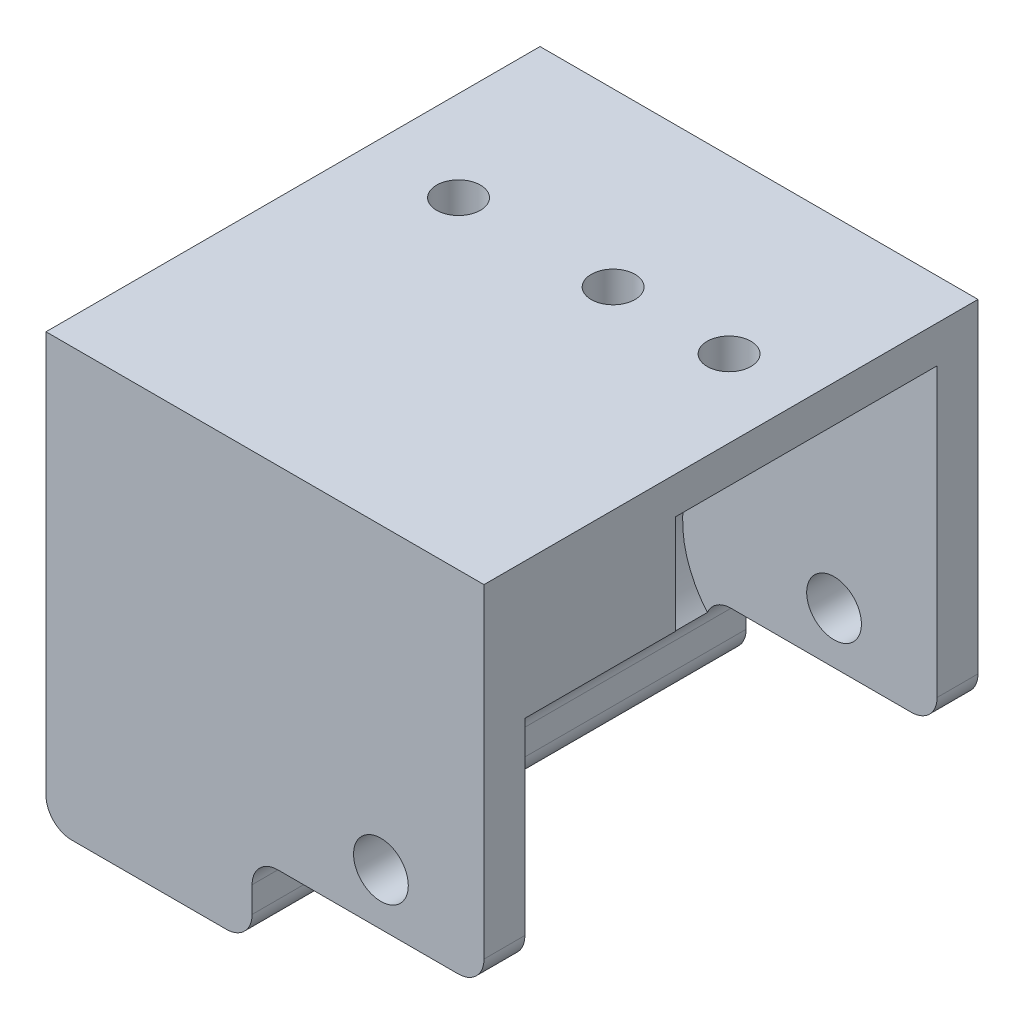
SolidWorks part; units mm, degrees
ref_plane "Front Plane" through (0, 0, 0) normal (0, 0, 1) x (1, 0, 0)
ref_plane "Top Plane" through (0, 0, 0) normal (0, 1, 0) x (1, 0, 0)
ref_plane "Right Plane" through (0, 0, 0) normal (1, 0, 0) x (0, 0, -1)
sketch "Sketch1" plane through (0, 0, 0) normal (0, 0, 1) x (1, 0, 0)
  line L0 (-18, 24) -> (-18, 0) construction
  line L5 (0, 0) -> (-18, 0)
  line L6 (0, 0) -> (0, 24)
  line L7 (0, 24) -> (-34, 24)
  line L8 (-34, 0) -> (-34, 24)
  line L11 (-34, 0) -> (-34, -6)
  line L12 (-34, -6) -> (-18, -6)
  line L13 (-18, 0) -> (-18, -6)
  circle A27 centre (-4, 19.15) radius 2.125 construction
  circle A28 centre (-12, 19.15) radius 2.125 construction
  circle A29 centre (-21, 19.15) radius 2.125 construction
  circle A30 centre (-8, 4) radius 2.125
  dimension "D3" = 4.25
  dimension "D7" = 8
  dimension "D8" = 4.25
  dimension "D1" = 4.25
  dimension "D2" = 4.25
  dimension "D4" = 4.85
  dimension "D5" = 9
  dimension "D9" = 4
  dimension "D6" = 4
  dimension "D10" = 4
  dimension "D11" = 24
  dimension "D12" = 13
  dimension "D13" = 16
  dimension "D14" = 30
extrude "Boss-Extrude1" add sketch "Sketch1" along normal blind 3.175
ref_plane "Plane1" through (0, 0, -16) normal (0, 0, -1) x (-1, 0, 0)
sketch "Sketch4" plane through (0, 24, 0) normal (0, 1, 0) x (1, 0, 0)
  line L0 (-34, 32) -> (0, 32) construction
  line L1 (-34, -3.175) -> (0, -3.175)
  line L2 (-34, -3.175) -> (-34, 35.175)
  line L3 (-34, 35.175) -> (0, 35.175)
  line L4 (0, -3.175) -> (0, 35.175)
  line L5 (0, 0) -> (-34, 0) construction
  dimension "D1" = 3.175
  dimension "D2" = 32
extrude "Boss-Extrude2" add sketch "Sketch4" along normal blind 3.175
mirror "Mirror2" about plane through (0, 0, -16) normal (0, 0, -1) of "Boss-Extrude1"
sketch "Sketch5" plane through (0, 0, 0) normal (0, 0, -1) x (-1, 0, 0)
  line L0 (0, 24) -> (34, 24) construction
  line L1 (0, 24) -> (34, 24) construction
  line L2 (18, 9) -> (18, 16.6)
  line L3 (34, -6) -> (18, -6)
  line L4 (34, -6) -> (34, 16.6)
  line L6 (18, -6) -> (18, -1)
  line L7 (18, 16.6) -> (34, 16.6)
  arc A1 (18, -1) -> (18, 9) centre (11.755, 4) ccw
  dimension "D3" = 8
  dimension "D1" = 16
  dimension "D2" = 5
  dimension "D4" = 10
  dimension "D5" = 22.6
  dimension "D6" = 0
extrude "Boss-Extrude3" add sketch "Sketch5" along normal up to next
fillet "Fillet1" radius 2 5 edges at (-18, 0, 1.5875) (0, 0, -33.5875) (0, 0, 1.5875) (-34, -6, -16) (-18, -6, -16)
sketch "Sketch6" plane through (0, 0, 0) normal (0, 0, -1) x (-1, 0, 0)
  line L3 (0, 24) -> (34, 24)
  line L4 (0, 24) -> (0, 16.6)
  line L5 (0, 16.6) -> (34, 16.6)
  line L6 (34, 24) -> (34, 16.6)
  dimension "D1" = 7.4
extrude "Boss-Extrude4" add sketch "Sketch6" along normal blind 11.7
sketch "Sketch7" plane through (0, 24, 0) normal (0, -1, 0) x (1, 0, 0)
  line L4 (0, -11.7) -> (-34, -11.7)
  line L5 (-34, -11.7) -> (-34, -32)
  line L6 (-34, -32) -> (0, -32)
  line L7 (0, -32) -> (0, -11.7)
  line L8 (0, -11.7) -> (-34, -11.7)
  line L9 (-34, -11.7) -> (-34, -32)
  line L10 (-34, -32) -> (0, -32)
  line L11 (0, -32) -> (0, -11.7)
  dimension "D1" = 0
extrude "Cut-Extrude1" cut sketch "Sketch7" against normal blind 0.3
sketch "Sketch9" plane through (0, 27.175, 0) normal (0, 1, 0) x (1, 0, 0)
  line L0 (-34, 21.85) -> (0, 21.85) construction
  line L4 (0, 11.7) -> (0, 32)
  line L5 (-34, 11.7) -> (0, 11.7)
  line L6 (-34, 32) -> (-34, 11.7)
  line L7 (0, 32) -> (-34, 32)
  line L8 (0, 11.7) -> (0, 32) construction
  line L9 (-34, 11.7) -> (0, 11.7) construction
  line L10 (-34, 32) -> (-34, 11.7) construction
  line L11 (0, 32) -> (-34, 32) construction
  circle A0 centre (-15, 21.85) radius 1.7
  circle A1 centre (-6, 21.85) radius 1.7
  circle A2 centre (-27, 21.85) radius 1.7
  dimension "D2" = 3.4
  dimension "D4" = 3.4
  dimension "D6" = 3.4
  dimension "D3" = 15
  dimension "D5" = 6
  dimension "D7" = 12
  dimension "D1" = 0
extrude "Cut-Extrude2" cut sketch "Sketch9" against normal through all
